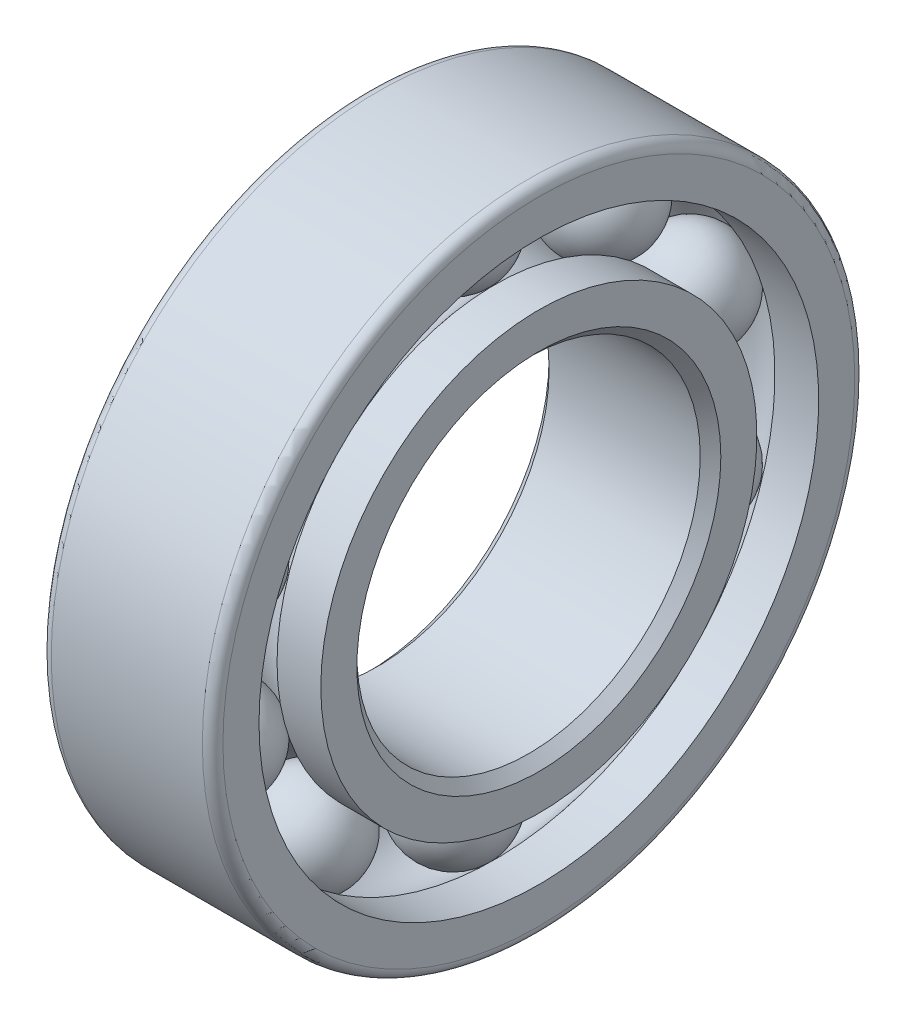
SolidWorks part; units mm, degrees
ref_plane "Front Plane" through (0, 0, 0) normal (0, 0, 1) x (1, 0, 0)
ref_plane "Top Plane" through (0, 0, 0) normal (0, 1, 0) x (1, 0, 0)
ref_plane "Right Plane" through (0, 0, 0) normal (1, 0, 0) x (0, 0, -1)
sketch "Sketch1" plane through (0, 0, 0) normal (0, 1, 0) x (1, 0, 0)
  line L0 (-10.3017, 0) -> (0, 0) construction
  line L1 (0, 0) -> (0, 8.825) construction
  line L3 (2.5, 9.5) -> (-2.5, 9.5)
  line L4 (2.5, 9.5) -> (2.5, 8.15)
  line L5 (2.5, 8.15) -> (-2.5, 8.15)
  line L6 (-2.5, 9.5) -> (-2.5, 8.15)
  line L7 (2.5, 9.5) -> (-2.5, 8.15) construction
  line L8 (2.5, 8.15) -> (-2.5, 9.5) construction
  line L9 (2.5, 6.35) -> (-2.5, 6.35)
  line L10 (2.5, 6.35) -> (2.5, 5)
  line L11 (2.5, 5) -> (-2.5, 5)
  line L12 (-2.5, 6.35) -> (-2.5, 5)
  line L13 (2.5, 6.35) -> (-2.5, 5) construction
  line L14 (2.5, 5) -> (-2.5, 6.35) construction
  circle A0 centre (0, 7.25) radius 1.5206
  point P9 (0, 5.675)
  dimension "D2" = 5
  dimension "D1" = 5
  dimension "D3" = 9.5
  dimension "D4" = 6.35
  dimension "D5" = 8.15
revolve "Revolve1" add sketch "Sketch1" angle 360 about L0 region at (0, 0, -8.904) region at (0, 0, -5.596)
ref_axis "Axis1" through (2.5, 0, 0) along (-1, 0, 0)
sketch "Sketch2" plane through (0, 0, 0) normal (0, 0, 1) x (1, 0, 0)
  line L0 (-1.5, 7.25) -> (1.5, 7.25)
  circle A0 centre (0, 7.25) radius 1.5
  point P4 (0, 0)
  point P5 (0, 0)
  dimension "D1" = 3
  dimension "D2" = 7.25
revolve "Revolve2" add sketch "Sketch2" angle 360 about L0 region at (0, 7.8866, 0)
pattern_circular "CirPattern2" count 10 over 360 about axis through (2.5, 0, 0) along (-1, 0, 0) of bodies 103
fillet "Fillet1" radius 0.3 2 edges at (2.5, 0, 9.5) (-2.5, 0, 9.5)
chamfer "Chamfer1" distance 0.3 angle 45 2 edges at (2.5, 0, 5) (-2.5, 0, 5)
